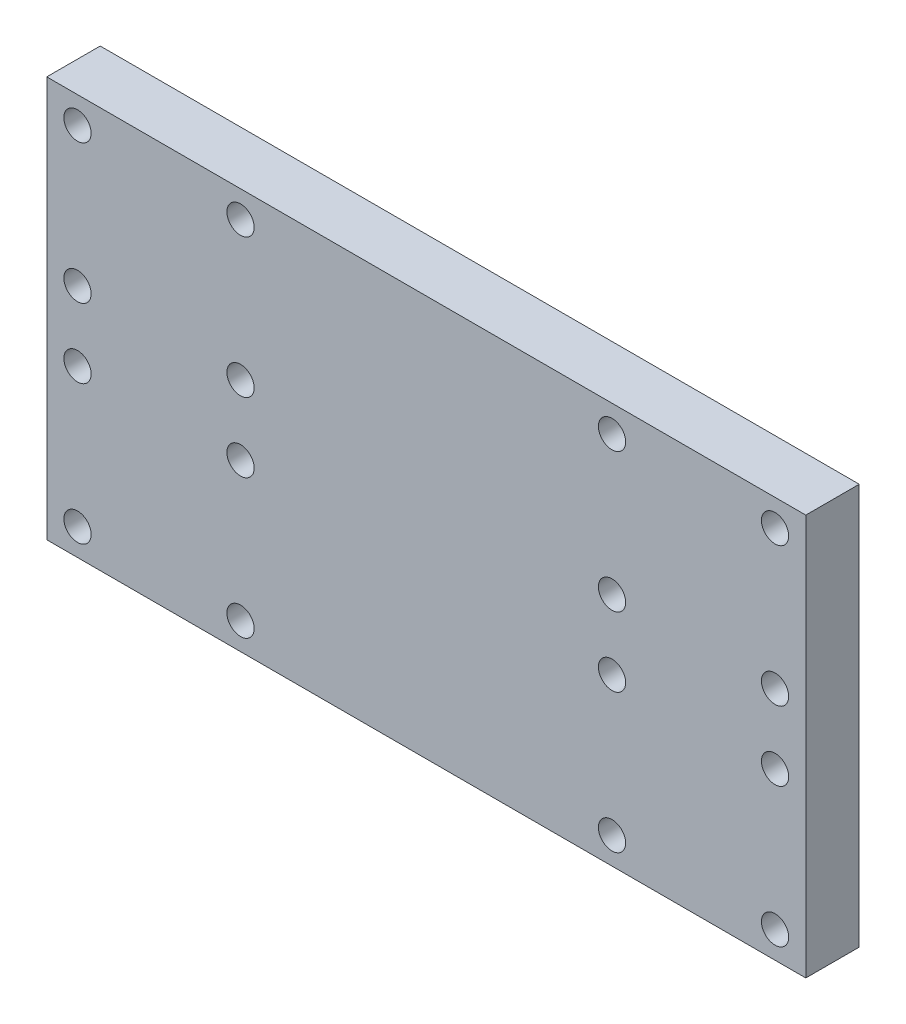
SolidWorks part; units mm, degrees
ref_plane "Front Plane" through (0, 0, 0) normal (0, 0, 1) x (1, 0, 0)
ref_plane "Top Plane" through (0, 0, 0) normal (0, 1, 0) x (1, 0, 0)
ref_plane "Right Plane" through (0, 0, 0) normal (1, 0, 0) x (0, 0, -1)
sketch "Sketch1" plane through (0, 0, 0) normal (0, 0, 1) x (1, 0, 0)
  line L1 (-71, -37.5) -> (71, -37.5)
  line L2 (-71, -37.5) -> (-71, 37.5)
  line L3 (-71, 37.5) -> (71, 37.5)
  line L4 (71, -37.5) -> (71, 37.5)
  line L5 (-71, -37.5) -> (71, 37.5) construction
  line L6 (-71, 37.5) -> (71, -37.5) construction
  point P0 (0, 0)
  dimension "D1" = 75
  dimension "D2" = 142
extrude "Boss-Extrude1" add sketch "Sketch1" along normal mid plane 10
sketch "Sketch2" plane through (0, 0, 5) normal (0, 0, 1) x (1, 0, 0)
  line L3 (-65.25, 37.5) -> (-65.25, -37.5)
  line L4 (-65.25, 37.5) -> (-65.25, -37.5) construction
  line L6 (65.25, -37.5) -> (65.25, 37.5)
  line L7 (65.25, -37.5) -> (65.25, 37.5) construction
  line L13 (-34.75, 37.5) -> (-34.75, -37.5)
  line L14 (-34.75, 37.5) -> (-34.75, -37.5) construction
  line L16 (34.75, -37.5) -> (34.75, 37.5)
  line L18 (34.75, -37.5) -> (34.75, 37.5) construction
  line L20 (71, 32.5) -> (-71, 32.5)
  line L21 (71, 32.5) -> (-71, 32.5) construction
  line L23 (-71, -32.5) -> (71, -32.5)
  line L24 (-71, -32.5) -> (71, -32.5) construction
  line L26 (71, 6.5) -> (-71, 6.5)
  line L27 (71, 6.5) -> (-71, 6.5) construction
  line L29 (-71, -6.5) -> (71, -6.5)
  line L30 (-71, -6.5) -> (71, -6.5) construction
  circle A0 centre (-65.25, 32.5) radius 2.55
  circle A1 centre (-34.75, 32.5) radius 2.55
  circle A2 centre (-34.75, 6.5) radius 2.55
  circle A3 centre (-65.25, 6.5) radius 2.55
  circle A4 centre (65.25, 32.5) radius 2.55
  circle A5 centre (65.25, 6.5) radius 2.55
  circle A6 centre (34.75, 6.5) radius 2.55
  circle A7 centre (34.75, 32.5) radius 2.55
  circle A8 centre (-65.25, -6.5) radius 2.55
  circle A9 centre (-34.75, -6.5) radius 2.55
  circle A10 centre (-34.75, -32.5) radius 2.55
  circle A11 centre (-65.25, -32.5) radius 2.55
  circle A12 centre (34.75, -6.5) radius 2.55
  circle A13 centre (65.25, -6.5) radius 2.55
  circle A14 centre (65.25, -32.5) radius 2.55
  circle A15 centre (34.75, -32.5) radius 2.55
  dimension "D9" = 5.1
  dimension "D10" = 5.1
  dimension "D11" = 5.1
  dimension "D12" = 5.1
  dimension "D13" = 5.1
  dimension "D14" = 5.1
  dimension "D15" = 5.1
  dimension "D16" = 5.1
  dimension "D17" = 5.1
  dimension "D18" = 5.1
  dimension "D19" = 5.1
  dimension "D20" = 5.1
  dimension "D21" = 5.1
  dimension "D22" = 5.1
  dimension "D23" = 5.1
  dimension "D24" = 5.1
  dimension "D1" = 5.75
  dimension "D2" = 5.75
  dimension "D3" = 36.25
  dimension "D4" = 36.25
  dimension "D5" = 5
  dimension "D6" = 5
  dimension "D7" = 31
  dimension "D8" = 31
extrude "Cut-Extrude1" cut sketch "Sketch2" against normal through all
